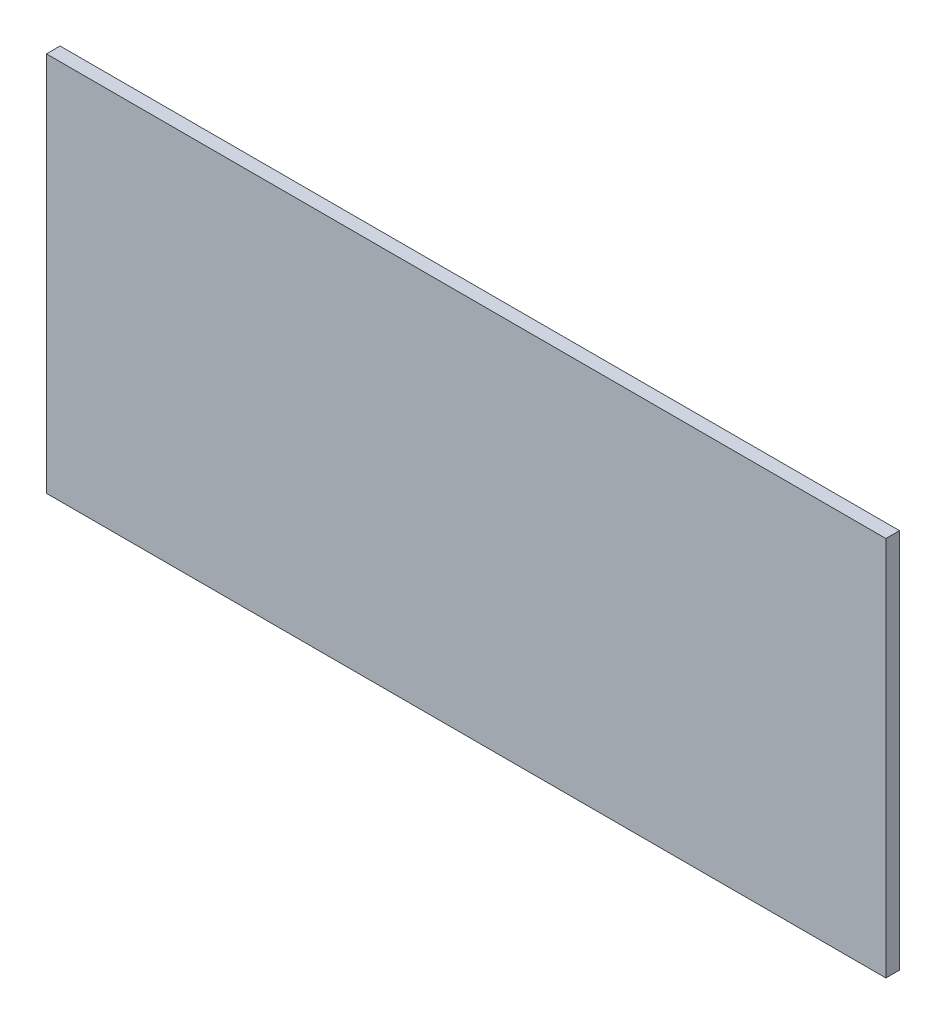
SolidWorks part; units mm, degrees
material "Thornel Mat VMA"
ref_plane "Front Plane" through (0, 0, 0) normal (0, 0, 1) x (1, 0, 0)
ref_plane "Top Plane" through (0, 0, 0) normal (0, 1, 0) x (1, 0, 0)
ref_plane "Right Plane" through (0, 0, 0) normal (1, 0, 0) x (0, 0, -1)
sketch "Sketch1" plane through (0, 0, 0) normal (0, 0, 1) x (1, 0, 0)
  line L1 (20.2869, 47.6) -> (204.7012, 47.6)
  line L2 (20.2869, 47.6) -> (20.2869, -36.0143)
  line L3 (20.2869, -36.0143) -> (204.7012, -36.0143)
  line L4 (204.7012, 47.6) -> (204.7012, -36.0143)
extrude "Boss-Extrude1" add sketch "Sketch1" along normal blind 3
